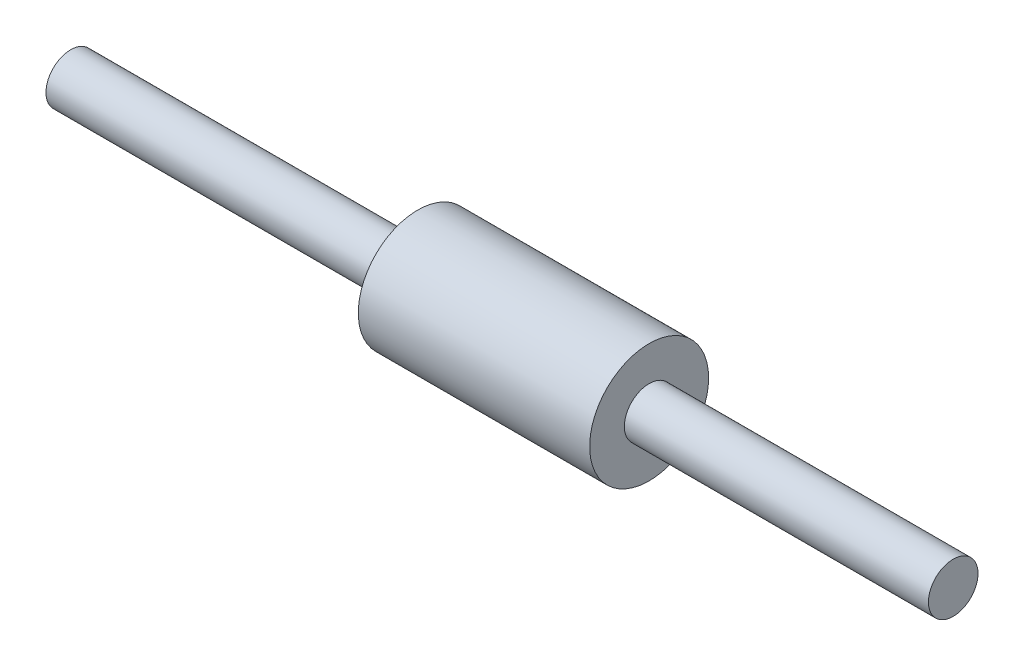
SolidWorks part; units mm, degrees
ref_plane "Front Plane" through (0, 0, 0) normal (0, 0, 1) x (1, 0, 0)
ref_plane "Top Plane" through (0, 0, 0) normal (0, 1, 0) x (1, 0, 0)
ref_plane "Right Plane" through (0, 0, 0) normal (1, 0, 0) x (0, 0, -1)
sketch "Sketch1" plane through (0, 0, 0) normal (0, 0, 1) x (1, 0, 0)
  line L0 (196.3562, 0) -> (-196.3562, 0) construction
  line L3 (127, 7.5) -> (-140, 7.5)
  line L4 (0, -42.6677) -> (0, 42.6677) construction
  line L7 (127, 7.5) -> (127, 0)
  line L8 (127, 0) -> (-127, 0)
  line L9 (-140, 7.5) -> (-140, 5.5)
  line L10 (-140, 5.5) -> (-127, 5.5)
  line L11 (-127, 5.5) -> (-127, 0)
  line L12 (-35, 18) -> (35, 18)
  line L13 (-35, 18) -> (-35, 7.5)
  line L14 (35, 18) -> (35, 7.5)
  point P3 (0, 18)
  point P10 (0, 0)
  dimension "D1" = 127
  dimension "D2" = 140
  dimension "D3" = 13
  dimension "D4" = 15
  dimension "D5" = 11
  dimension "D6" = 36
  dimension "D7" = 70
revolve "Revolve1" add sketch "Sketch1" angle 360 about L0 region at (-1.7975, 3.787, 0) region at (0, 12.75, 0)
